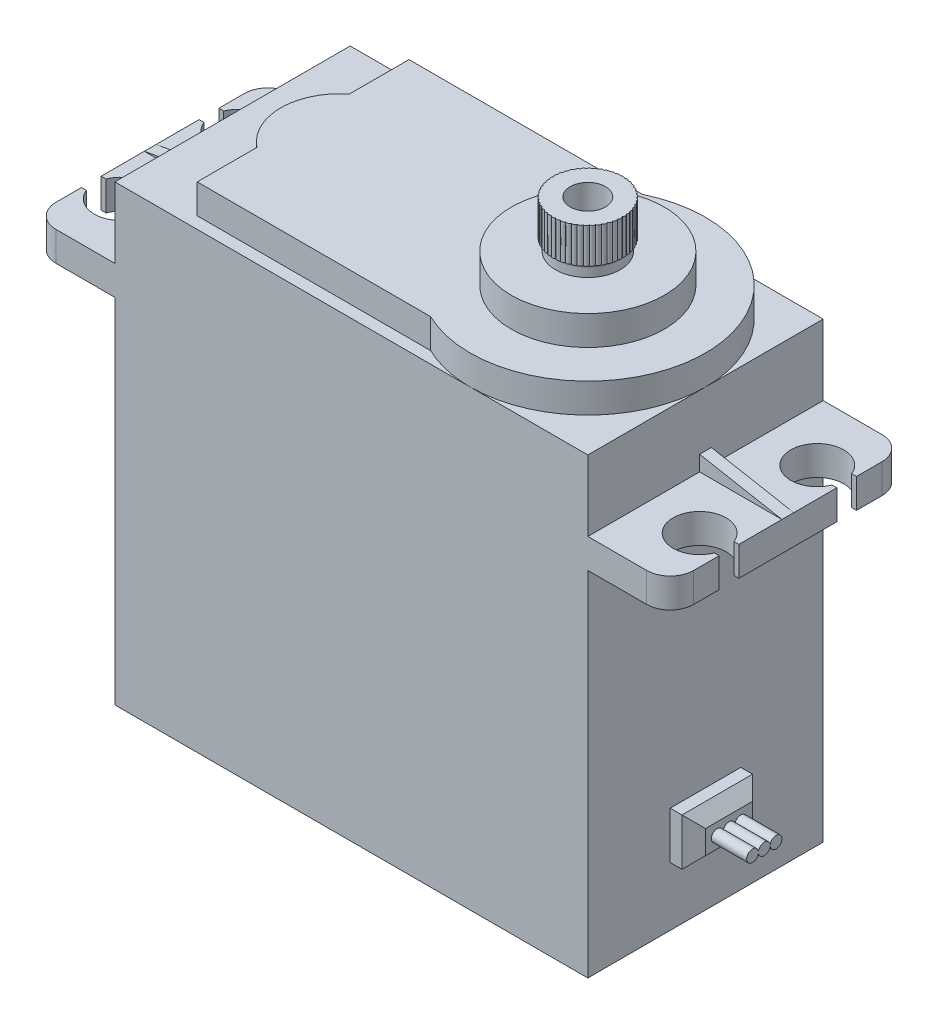
SolidWorks part; units mm, degrees
ref_plane "前视基准面" through (0, 0, 0) normal (0, 0, 1) x (1, 0, 0)
ref_plane "上视基准面" through (0, 0, 0) normal (0, 1, 0) x (1, 0, 0)
ref_plane "右视基准面" through (0, 0, 0) normal (1, 0, 0) x (0, 0, -1)
sketch "草图1" plane through (0, 0, 0) normal (0, 1, 0) x (1, 0, 0)
  line L1 (-20.1, 10) -> (20.1, 10)
  line L2 (-20.1, 10) -> (-20.1, -10)
  line L3 (-20.1, -10) -> (20.1, -10)
  line L4 (20.1, 10) -> (20.1, -10)
  line L5 (-20.1, 10) -> (20.1, -10) construction
  line L6 (-20.1, -10) -> (20.1, 10) construction
  point P0 (0, 0)
  dimension "D1" = 40.2
  dimension "D2" = 20
extrude "凸台-拉伸1" add sketch "草图1" along normal blind 8.5 and the other way blind 30
sketch "草图2" plane through (0, 0, 0) normal (0, 1, 0) x (1, 0, 0)
  line L1 (20.1, 10) -> (27.1, 10)
  line L2 (20.1, 10) -> (20.1, -10)
  line L3 (20.1, -10) -> (27.1, -10)
  line L4 (27.1, 10) -> (27.1, -10)
  dimension "D1" = 7
extrude "凸台-拉伸2" add sketch "草图2" along normal blind 2.5
sketch "草图3" plane through (0, 2.5, 0) normal (0, 1, 0) x (1, 0, 0)
  line L0 (-21.175, 0) -> (21.175, 0) construction
  line L1 (26.6886, 4.1631) -> (27.1, 4.1631)
  line L3 (26.6886, 5.8369) -> (27.1, 5.8369)
  line L4 (20.1, 10) -> (20.1, -10)
  line L5 (20.1, -10) -> (27.1, -10)
  line L6 (27.1, -10) -> (27.1, 10)
  line L7 (27.1, 10) -> (20.1, 10)
  line L10 (27.1, -5.8369) -> (27.1, -4.1631)
  line L13 (26.6886, -4.1631) -> (27.1, -4.1631)
  line L14 (26.6886, -5.8369) -> (27.1, -5.8369)
  line L15 (27.1, 4.1631) -> (27.1, 5.8369)
  line L16 (20.1, 10) -> (20.1, -10) construction
  arc A0 (26.6886, 5.8369) -> (26.6886, 4.1631) centre (24.6, 5) ccw
  arc A1 (26.6886, -5.8369) -> (26.6886, -4.1631) centre (24.6, -5) cw
  point P6 (25.6289, 5)
  dimension "D4" = 4.5
  dimension "D2" = 4.5
  dimension "D3" = 5
  dimension "D1" = 0
extrude "切除-拉伸1" cut sketch "草图3" against normal blind 2.5
mirror "镜向1" about plane through (0, 0, 0) normal (1, 0, 0) of "切除-拉伸1", "凸台-拉伸2"
fillet "圆角1" radius 2 4 edges at (-27.1, 1.25, 10) (-27.1, 1.25, -10) (27.1, 1.25, -10) (27.1, 1.25, 10)
sketch "草图4" plane through (0, 8.5, 0) normal (0, 1, 0) x (1, 0, 0)
  line L0 (20.1, 10) -> (-20.1, 10) construction
  line L1 (-20.1, -10) -> (20.1, -10) construction
  line L2 (20.1, -10) -> (20.1, 10) construction
  line L3 (-20.1, 10) -> (-20.1, -10) construction
  line L4 (-14.1, -9) -> (5.7411, -9)
  line L5 (-14.1, -9) -> (-14.1, -3.923)
  line L6 (-14.1, 9) -> (5.7411, 9)
  line L8 (-14.1, -9) -> (14.1, 9) construction
  line L9 (-14.1, 9) -> (14.1, -9) construction
  line L10 (-14.1, 3.923) -> (-14.1, 9)
  arc A0 (0.1002, 0.064) -> (0.1002, -0.064) centre (10.1, 0) ccw
  arc A1 (-14.1, 3.923) -> (-14.1, -3.923) centre (-11, 0) ccw
  arc A2 (5.7411, -9) -> (5.7411, 9) centre (10.1, 0) ccw
  point P8 (0, 0)
  dimension "D3" = 10
  dimension "D1" = 6
  dimension "D2" = 1
  dimension "D4" = 11
extrude "凸台-拉伸3" add sketch "草图4" along normal blind 2.5 contours A2 L6 L10 A1 L5 L4 region at (2.0972, 8.5, 0)
sketch "草图5" plane through (0, 11, 0) normal (0, 1, 0) x (1, 0, 0)
  arc A0 (5.7411, -9) -> (5.7411, 9) centre (10.1, 0) ccw construction
  arc A1 (5.7411, -9) -> (5.7411, 9) centre (10.1, 0) ccw
  circle A2 centre (10.1, 0) radius 6.5
  dimension "D1" = 13
extrude "凸台-拉伸4" add sketch "草图5" along normal blind 2.5 contours A2 region at (10.1, 11, 0)
sketch "草图6" plane through (0, 13.5, 0) normal (0, 1, 0) x (1, 0, 0)
  circle A0 centre (10.1, 0) radius 3
  dimension "D1" = 6
extrude "凸台-拉伸5" add sketch "草图6" along normal blind 4
sketch "草图7" plane through (0, 17.5, 0) normal (0, 1, 0) x (1, 0, 0)
  circle A0 centre (10.1, 0) radius 2.75 construction
  circle A1 centre (10.1, 0) radius 3
  circle A2 centre (10.1, 0) radius 3
  arc A3 (10.2837, 2.9196) -> (9.9163, 2.9196) centre (10.1, 2.75) ccw
  arc A4 (10.6482, 2.8735) -> (10.2837, 2.9196) centre (10.4447, 2.7283) ccw
  arc A5 (11.004, 2.7822) -> (10.6482, 2.8735) centre (10.7839, 2.6636) ccw
  arc A6 (11.3456, 2.6469) -> (11.004, 2.7822) centre (11.1123, 2.5569) ccw
  arc A7 (11.6675, 2.47) -> (11.3456, 2.6469) centre (11.4248, 2.4098) ccw
  arc A8 (11.9647, 2.254) -> (11.6675, 2.47) centre (11.7164, 2.2248) ccw
  arc A9 (12.2325, 2.0025) -> (11.9647, 2.254) centre (11.9825, 2.0047) ccw
  arc A10 (12.4667, 1.7195) -> (12.2325, 2.0025) centre (12.2189, 1.7529) ccw
  arc A11 (12.6635, 1.4093) -> (12.4667, 1.7195) centre (12.4219, 1.4735) ccw
  arc A12 (12.8199, 1.0769) -> (12.6635, 1.4093) centre (12.5883, 1.1709) ccw
  arc A13 (12.9335, 0.7275) -> (12.8199, 1.0769) centre (12.7154, 0.8498) ccw
  arc A14 (13.0023, 0.3666) -> (12.9335, 0.7275) centre (12.8013, 0.5153) ccw
  arc A15 (13.0254, 0) -> (13.0023, 0.3666) centre (12.8446, 0.1727) ccw
  arc A16 (13.0023, -0.3666) -> (13.0254, 0) centre (12.8446, -0.1727) ccw
  arc A17 (12.9335, -0.7275) -> (13.0023, -0.3666) centre (12.8013, -0.5153) ccw
  arc A18 (12.8199, -1.0769) -> (12.9335, -0.7275) centre (12.7154, -0.8498) ccw
  arc A19 (12.6635, -1.4093) -> (12.8199, -1.0769) centre (12.5883, -1.1709) ccw
  arc A20 (12.4667, -1.7195) -> (12.6635, -1.4093) centre (12.4219, -1.4735) ccw
  arc A21 (12.2325, -2.0025) -> (12.4667, -1.7195) centre (12.2189, -1.7529) ccw
  arc A22 (11.9647, -2.254) -> (12.2325, -2.0025) centre (11.9825, -2.0047) ccw
  arc A23 (11.6675, -2.47) -> (11.9647, -2.254) centre (11.7164, -2.2248) ccw
  arc A24 (11.3456, -2.6469) -> (11.6675, -2.47) centre (11.4248, -2.4098) ccw
  arc A25 (11.004, -2.7822) -> (11.3456, -2.6469) centre (11.1123, -2.5569) ccw
  arc A26 (10.6482, -2.8735) -> (11.004, -2.7822) centre (10.7839, -2.6636) ccw
  arc A27 (10.2837, -2.9196) -> (10.6482, -2.8735) centre (10.4447, -2.7283) ccw
  arc A28 (9.9163, -2.9196) -> (10.2837, -2.9196) centre (10.1, -2.75) ccw
  arc A29 (9.5518, -2.8735) -> (9.9163, -2.9196) centre (9.7553, -2.7283) ccw
  arc A30 (9.196, -2.7822) -> (9.5518, -2.8735) centre (9.4161, -2.6636) ccw
  arc A31 (8.8544, -2.6469) -> (9.196, -2.7822) centre (9.0877, -2.5569) ccw
  arc A32 (8.5325, -2.47) -> (8.8544, -2.6469) centre (8.7752, -2.4098) ccw
  arc A33 (8.2353, -2.254) -> (8.5325, -2.47) centre (8.4836, -2.2248) ccw
  arc A34 (7.9675, -2.0025) -> (8.2353, -2.254) centre (8.2175, -2.0047) ccw
  arc A35 (7.7333, -1.7195) -> (7.9675, -2.0025) centre (7.9811, -1.7529) ccw
  arc A36 (7.5365, -1.4093) -> (7.7333, -1.7195) centre (7.7781, -1.4735) ccw
  arc A37 (7.3801, -1.0769) -> (7.5365, -1.4093) centre (7.6117, -1.1709) ccw
  arc A38 (7.2665, -0.7275) -> (7.3801, -1.0769) centre (7.4846, -0.8498) ccw
  arc A39 (7.1977, -0.3666) -> (7.2665, -0.7275) centre (7.3987, -0.5153) ccw
  arc A40 (7.1746, 0) -> (7.1977, -0.3666) centre (7.3554, -0.1727) ccw
  arc A41 (7.1977, 0.3666) -> (7.1746, 0) centre (7.3554, 0.1727) ccw
  arc A42 (7.2665, 0.7275) -> (7.1977, 0.3666) centre (7.3987, 0.5153) ccw
  arc A43 (7.3801, 1.0769) -> (7.2665, 0.7275) centre (7.4846, 0.8498) ccw
  arc A44 (7.5365, 1.4093) -> (7.3801, 1.0769) centre (7.6117, 1.1709) ccw
  arc A47 (8.2353, 2.254) -> (7.9675, 2.0025) centre (8.2175, 2.0047) ccw
  arc A48 (8.5325, 2.47) -> (8.2353, 2.254) centre (8.4836, 2.2248) ccw
  arc A49 (8.8544, 2.6469) -> (8.5325, 2.47) centre (8.7752, 2.4098) ccw
  arc A50 (9.196, 2.7822) -> (8.8544, 2.6469) centre (9.0877, 2.5569) ccw
  arc A51 (9.5518, 2.8735) -> (9.196, 2.7822) centre (9.4161, 2.6636) ccw
  arc A52 (9.9163, 2.9196) -> (9.5518, 2.8735) centre (9.7553, 2.7283) ccw
  arc A53 (7.7333, 1.7195) -> (7.5365, 1.4093) centre (7.7781, 1.4735) ccw
  arc A55 (8.0259, 1.507) -> (7.9215, 1.6783) centre (7.7781, 1.4735) ccw [skipped]
  arc A65 (7.9675, 2.0025) -> (7.7333, 1.7195) centre (7.9811, 1.7529) ccw
  arc A73 (8.2311, 1.755) -> (8.149, 1.9381) centre (7.9811, 1.7529) ccw [skipped]
  circle M6 centre (10.1, 0) radius 3
  dimension "D2" = 5.5
  dimension "D1" = 0
  dimension "D3" = 50
extrude "切除-拉伸2" cut sketch "草图7" against normal blind 3 contours A50 A2 A49 | A51 A2 A50 | A52 A2 A51 | A52 A3 M6 | A4 A2 A3 | A5 A2 A4 | A6 A2 A5 | A48 A2 A47 | A49 A2 A48 | A65 A47 A2 | A65 A53 M6 | A53 A44 M6 | A43 A2 A42 | A42 A2 A41 | A44 A2 A43 | A41 A2 A40 | A40 A2 A39 | A39 A2 A38 | A38 A2 A37 | A37 A2 A36 | A36 A2 A35 | A35 A2 A34 | A34 A2 A33 | A33 A2 A32 | A32 A2 A31 | A31 A2 A30 | A30 A2 A29 | A29 A2 A28 | A28 A2 A27 | A27 A2 A26 | A26 A2 A25 | A25 A2 A24 | A24 A2 A23 | A23 A2 A22 | A22 A2 A21 | A21 A2 A20 | A20 A2 A19 | A19 A2 A18 | A18 A2 A17 | A17 A2 A16 | A16 A2 A15 | A15 A2 A14 | A14 A2 A13 | A13 A2 A12 | A12 A2 A11 | A11 A2 A10 | A10 A2 A9 | A9 A2 A8 | A8 A2 A7 | A7 A2 A6 region at (13.0777, 17.5, 0) region at (13.0543, 17.5, -0.3732) region at (13.0543, 17.5, 0.3732) region at (12.9842, 17.5, -0.7405) region at (12.9842, 17.5, 0.7405) region at (12.8686, 17.5, -1.0962) region at (12.8686, 17.5, 1.0962) region at (12.7094, 17.5, -1.4345) region at (12.7094, 17.5, 1.4345) region at (12.509, 17.5, -1.7503) region at (12.509, 17.5, 1.7503) region at (12.2707, 17.5, -2.0384) region at (12.2707, 17.5, 2.0384) region at (11.9981, 17.5, -2.2944) region at (11.9981, 17.5, 2.2944) region at (11.6956, 17.5, -2.5142) region at (11.6956, 17.5, 2.5142) region at (11.3679, 17.5, -2.6943) region at (11.3679, 17.5, 2.6943) region at (11.0202, 17.5, -2.832) region at (11.0202, 17.5, 2.832) region at (10.658, 17.5, -2.925) region at (10.658, 17.5, 2.925) region at (10.287, 17.5, -2.9719) region at (10.287, 17.5, 2.9719) region at (9.913, 17.5, -2.9719) region at (9.913, 17.5, 2.9719) region at (9.542, 17.5, -2.925) region at (9.542, 17.5, 2.925) region at (9.1798, 17.5, -2.832) region at (9.1798, 17.5, 2.832) region at (8.8321, 17.5, -2.6943) region at (8.8321, 17.5, 2.6943) region at (8.5044, 17.5, -2.5142) region at (8.5044, 17.5, 2.5142) region at (8.2019, 17.5, -2.2944) region at (8.2019, 17.5, 2.2944) region at (7.9293, 17.5, -2.0384) region at (7.9293, 17.5, 2.0384) region at (7.691, 17.5, -1.7503) region at (7.691, 17.5, 1.7503) region at (7.4906, 17.5, -1.4345) region at (7.4906, 17.5, 1.4345) region at (7.3314, 17.5, -1.0962) region at (7.3314, 17.5, 1.0962) region at (7.2158, 17.5, -0.7405) region at (7.2158, 17.5, 0.7405) region at (7.1457, 17.5, -0.3732) region at (7.1457, 17.5, 0.3732) region at (7.1223, 17.5, 0)
sketch "草图8" plane through (0, 13.5, 0) normal (0, 1, 0) x (1, 0, 0)
  circle A0 centre (10.1, 0) radius 3 construction
  circle A1 centre (10.1, 0) radius 3
  circle A2 centre (10.1, 0) radius 2.75
  circle A3 centre (10.1, 0) radius 3
  circle M3 centre (10.1, 0) radius 3
  dimension "D1" = 5.5
extrude "切除-拉伸4" cut sketch "草图8" along normal blind 1 contours A2 M3 region at (7.1849, 13.5, 0)
fillet "圆角2" radius 0.23 1 edges at (10.1, 14.5, 2.75)
sketch "草图9" plane through (20.1, 0, 0) normal (1, 0, 0) x (0, 0, -1)
  line L0 (-10, -30) -> (10, -30) construction
  line L1 (-3, -21) -> (3, -21)
  line L2 (-3, -21) -> (-3, -25)
  line L3 (-3, -25) -> (3, -25)
  line L4 (3, -21) -> (3, -25)
  line L5 (-3, -21) -> (3, -25) construction
  line L6 (-3, -25) -> (3, -21) construction
  point P0 (0, -23)
  dimension "D1" = 6
  dimension "D2" = 4
  dimension "D3" = 5
extrude "凸台-拉伸6" add sketch "草图9" along normal blind 2
chamfer "倒角1" distance 1 angle 45 4 edges at (22.1, -23, -3) (22.1, -25, 0) (22.1, -23, 3) (22.1, -21, 0)
sketch "草图10" plane through (22.1, 0, 0) normal (1, 0, 0) x (0, 0, -1)
  line L0 (2, -22) -> (-2, -22) construction
  line L1 (-2, -22) -> (-2, -24) construction
  line L2 (0.492, -22.9111) -> (0.508, -22.9111)
  line L3 (-0.508, -23.0889) -> (-0.492, -23.0889)
  line L5 (-0.508, -22.9111) -> (-0.492, -22.9111)
  line L7 (-0.502, -23.0446) -> (-0.498, -23.0443) construction
  line L8 (-0.502, -22.9554) -> (-0.498, -22.9557) construction
  line L9 (0.498, -23.0443) -> (0.502, -23.0446) construction
  line L10 (0.498, -22.9557) -> (0.502, -22.9554) construction
  line L11 (0.492, -23.0889) -> (0.508, -23.0889)
  arc A0 (-0.492, -23.0889) -> (0.492, -23.0889) centre (0, -23) ccw
  arc A1 (0.508, -23.0889) -> (0.508, -22.9111) centre (1, -23) ccw
  arc A2 (-0.508, -22.9111) -> (-0.508, -23.0889) centre (-1, -23) ccw
  arc A3 (0.492, -22.9111) -> (-0.492, -22.9111) centre (0, -23) ccw
  point P9 (0, -22)
  point P12 (-2, -23)
  dimension "D1" = 1
extrude "凸台-拉伸8" add sketch "草图10" along normal blind 3
sketch "草图11" plane through (0, 17.5, 0) normal (0, 1, 0) x (1, 0, 0)
  circle A1 centre (10.1, 0) radius 1.5
  dimension "D1" = 3
extrude "切除-拉伸5" cut sketch "草图11" against normal blind 3
sketch "草图13" plane through (0, 0, 0) normal (0, 0, 1) x (1, 0, 0)
  line L0 (20.1, 3.8) -> (20.1, 2.5)
  line L1 (20.1, 2.5) -> (20.1, 8.5) construction
  line L2 (20.1, 2.5) -> (27.1, 2.5)
  line L3 (27.1, 2.5) -> (20.1, 3.8)
  dimension "D1" = 1.3
extrude "凸台-拉伸9" add sketch "草图13" along normal blind 0.5 and the other way blind 0.5
mirror "镜向2" about plane through (0, 0, 0) normal (1, 0, 0) of "凸台-拉伸9"
